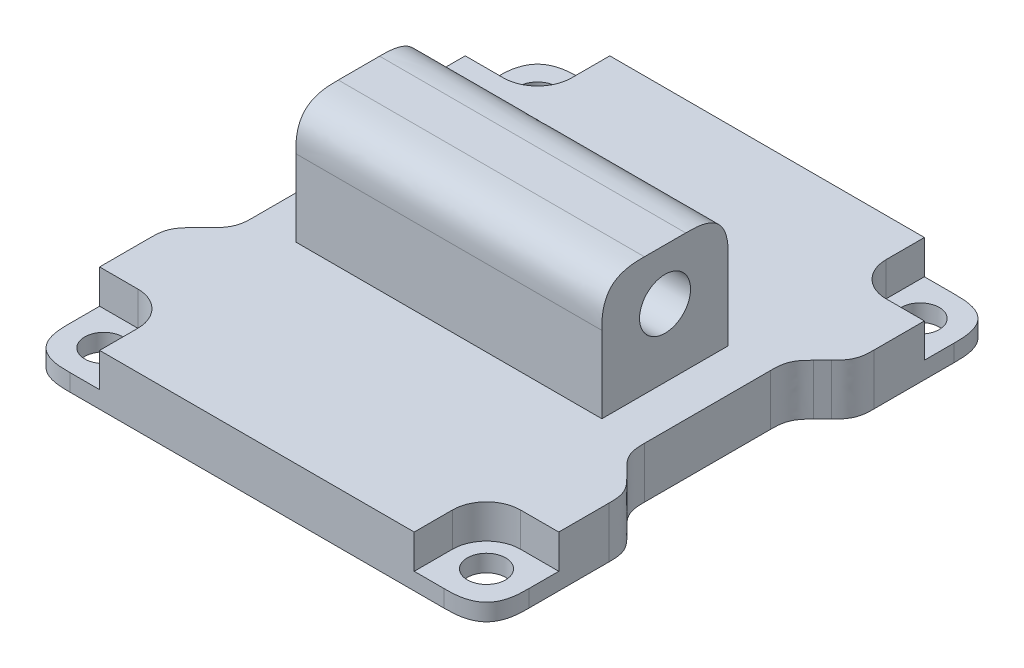
SolidWorks part; units mm, degrees
ref_plane "Front Plane" through (0, 0, 0) normal (0, 0, 1) x (1, 0, 0)
ref_plane "Top Plane" through (0, 0, 0) normal (0, 1, 0) x (1, 0, 0)
ref_plane "Right Plane" through (0, 0, 0) normal (1, 0, 0) x (0, 0, -1)
sketch "Sketch1" plane through (0, 0, 0) normal (0, 1, 0) x (1, 0, 0)
  line L15 (-27, -30) -> (27, -30)
  line L16 (-27, -30) -> (-27, 30)
  line L17 (-27, 30) -> (27, 30)
  line L18 (27, -30) -> (27, 30)
  line L19 (-27, -30) -> (27, 30) construction
  line L20 (-27, 30) -> (27, -30) construction
  point P0 (0, 0)
  dimension "D1" = 54
  dimension "D2" = 60
extrude "Boss-Extrude1" add sketch "Sketch1" along normal blind 6
hole_wizard "CBORE for M4 SHCS1" positions "Sketch2" profile "Sketch3" counterbore size "M4" standard "ANSI Metric"
sketch "Sketch2" plane through (0, 6, 0) normal (0, 1, 0) x (1, 0, 0)
  line L0 (-22.5, 25.5) -> (-22.5, -25.5) construction
  line L2 (0, -2.75) -> (0, 2.75) construction
  point P0 (-22.5, 25.5)
  point P2 (-22.5, -25.5)
  point P11 (-22.5, 0)
  point P12 (0, 0)
  point P15 (22.5, -25.5)
  point P16 (22.5, 25.5)
  dimension "D1" = 22.5
  dimension "D2" = 51
sketch "Sketch3" plane through (-22.5, 6, -25.5) normal (1, 0, 0) x (0, 0, 1)
  line L0 (0, 0) -> (0, 13.7519)
  line L1 (0, 13.7519) -> (2.25, 12.4)
  line L2 (2.25, 12.4) -> (2.25, 4)
  line L3 (2.25, 4) -> (4, 4)
  line L4 (4, 4) -> (4, 0)
  line L5 (4, 0) -> (0, 0)
  line L10 (0, 13.7519) -> (-2.25, 12.4) construction
  line L11 (0, -6.35) -> (0, 107.95) construction
  dimension "Hole Dia." = 4.5
  dimension "Hole Depth" = 12.4
  dimension "C'Bore Dia." = 8
  dimension "C'Bore Depth" = 4
  dimension "Drill Angle" = 118
sketch "Sketch4" plane through (0, 6, 0) normal (0, 1, 0) x (1, 0, 0)
  line L0 (-22.5, 21.5) -> (-27, 21.5)
  line L1 (-27, 30) -> (-27, -30) construction
  line L2 (-27, 21.5) -> (-27, 30)
  line L3 (-27, 30) -> (-18.5, 30)
  line L4 (27, 30) -> (-27, 30) construction
  line L5 (-18.5, 30) -> (-18.5, 25.5)
  line L6 (0, -2.75) -> (0, 2.75) construction
  line L7 (22.5, 21.5) -> (27, 21.5)
  line L8 (27, 21.5) -> (27, 30)
  line L9 (27, 30) -> (18.5, 30)
  line L10 (18.5, 30) -> (18.5, 25.5)
  line L11 (-2.75, 0) -> (2.75, 0) construction
  line L12 (18.5, -30) -> (18.5, -25.5)
  line L13 (27, -30) -> (18.5, -30)
  line L14 (27, -21.5) -> (27, -30)
  line L15 (22.5, -21.5) -> (27, -21.5)
  line L16 (-18.5, -30) -> (-18.5, -25.5)
  line L17 (-27, -30) -> (-18.5, -30)
  line L18 (-27, -21.5) -> (-27, -30)
  line L19 (-22.5, -21.5) -> (-27, -21.5)
  circle A0 centre (-22.5, 25.5) radius 4 construction
  arc A1 (-22.5, 21.5) -> (-18.5, 25.5) centre (-22.5, 25.5) ccw
  arc A2 (22.5, 21.5) -> (18.5, 25.5) centre (22.5, 25.5) cw
  arc A3 (22.5, -21.5) -> (18.5, -25.5) centre (22.5, -25.5) ccw
  arc A4 (-22.5, -21.5) -> (-18.5, -25.5) centre (-22.5, -25.5) cw
extrude "Cut-Extrude1" cut sketch "Sketch4" against normal up to surface (4 mm away) up to face at (22.5, 2, -23.25)
fillet "Fillet1" radius 5 4 edges at (27, 1, -30) (-27, 1, -30) (-27, 1, 30) (27, 1, 30) curvature continuous yes
sketch "Sketch5" plane through (0, 6, 0) normal (0, 1, 0) x (1, 0, 0)
  line L0 (-27, 13.5) -> (-23, 9.5)
  line L1 (-27, 21.5) -> (-27, -21.5) construction
  line L2 (-23, 9.5) -> (-23, -9.5)
  line L3 (-23, -9.5) -> (-27, -13.5)
  line L4 (-27, 13.5) -> (-27, -13.5)
  line L5 (-27, 21.5) -> (-22.5, 21.5) construction
  line L6 (-22.5, -21.5) -> (-27, -21.5) construction
  line L7 (0, -3.3275) -> (0, 3.3275) construction
  line L8 (27, 13.5) -> (23, 9.5)
  line L9 (23, 9.5) -> (23, -9.5)
  line L10 (23, -9.5) -> (27, -13.5)
  line L11 (27, 13.5) -> (27, -13.5)
  point P4 (-24.023, -12.8241)
  point P7 (-23, 13.4218)
  dimension "D1" = 45
  dimension "D2" = 4
  dimension "D3" = 8
  dimension "D4" = 8
extrude "Cut-Extrude2" cut sketch "Sketch5" against normal through all
fillet "Fillet2" radius 5 8 edges at (27, 3, 13.5) (27, 3, -13.5) (-27, 3, 13.5) (-27, 3, -13.5) (-23, 3, 9.5) (23, 3, 9.5) (23, 3, -9.5) (-23, 3, -9.5) curvature continuous yes
sketch "Sketch6" plane through (-23, 0, 0) normal (-1, 0, 0) x (0, 0, 1)
  line L0 (7.4289, 6) -> (-7.4289, 6) construction
  line L2 (-7.4289, 6) -> (7.4289, 6)
  line L3 (-7.4289, 6) -> (-7.4289, 20)
  line L4 (-7.4289, 20) -> (7.4289, 20)
  line L5 (7.4289, 6) -> (7.4289, 20)
  circle A0 centre (0, 14) radius 3
  point P4 (0, 0)
  point P10 (0, 0)
  point P11 (7.4289, 6)
  dimension "D1" = 6
  dimension "D2" = 8
  dimension "D3" = 6
extrude "Boss-Extrude2" add sketch "Sketch6" against normal offset from surface (36 mm away) 5 from offset 5 up to face at (23, 3, 0) offset against normal yes
fillet "Fillet3" radius 5 2 edges at (0, 20, -7.4289) (0, 20, 7.4289) curvature continuous yes
